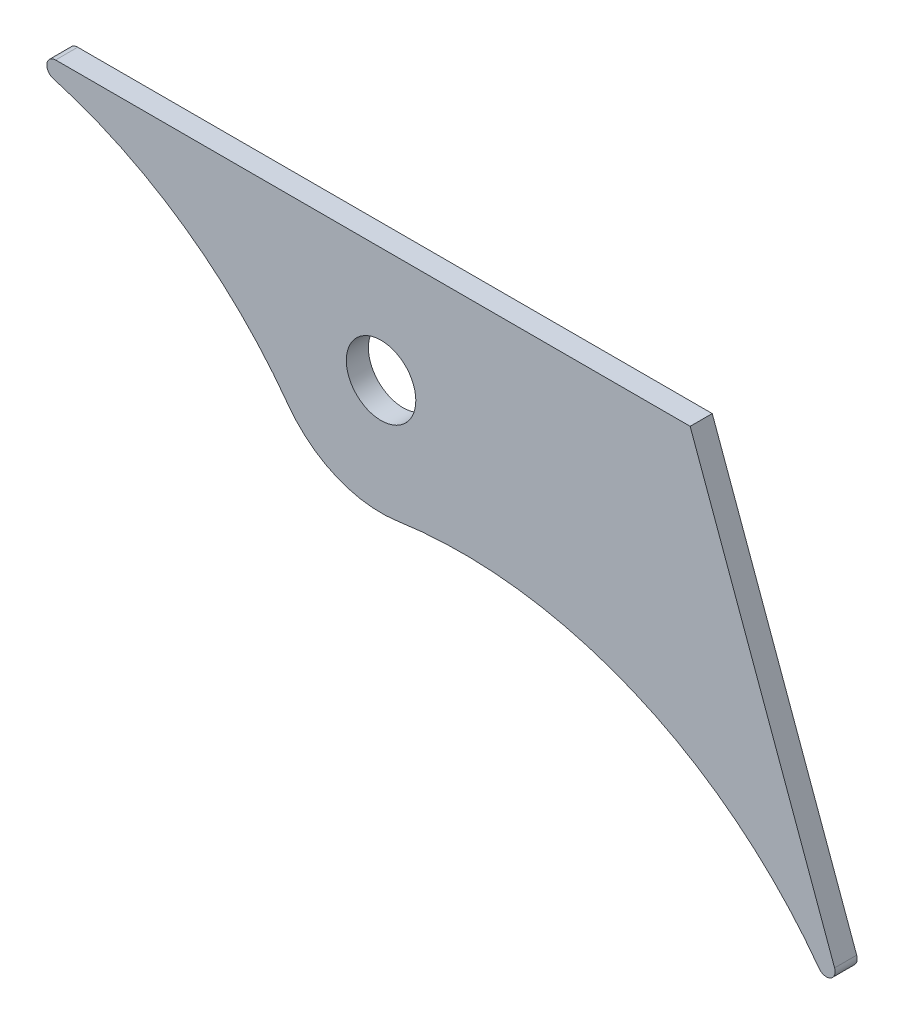
SolidWorks part; units mm, degrees
material "6061 Alloy"
ref_plane "Front Plane" through (0, 0, 0) normal (0, 0, 1) x (1, 0, 0)
ref_plane "Top Plane" through (0, 0, 0) normal (0, 1, 0) x (1, 0, 0)
ref_plane "Right Plane" through (0, 0, 0) normal (1, 0, 0) x (0, 0, -1)
sketch "Sketch1" plane through (0, 0, 0) normal (0, 0, 1) x (1, 0, 0)
  line L0 (0, 0) -> (-44.45, 0)
  line L1 (0, 0) -> (26.913, -73.9428)
  line L2 (-44.45, 0) -> (-109.2075, 0)
  circle A0 centre (-44.45, -16.51) radius 5
  arc A1 (-57.8127, -26.2063) -> (-42.0373, -32.8428) centre (-44.45, -16.51) ccw
  arc A2 (26.913, -73.9428) -> (-42.0373, -32.8428) centre (-32.7575, -95.661) ccw
  arc A3 (-57.8127, -26.2063) -> (-109.2075, 0) centre (-109.2075, -63.5) ccw
  dimension "D2" = 10
  dimension "D5" = 63.5
  dimension "D6" = 63.5
  dimension "D1" = 110
  dimension "D3" = 16.51
  dimension "D4" = 44.45
extrude "Boss-Extrude1" add sketch "Sketch1" along normal blind 3.175
fillet "Fillet1" radius 1.27 2 edges at (26.913, -73.9428, 1.5875) (-109.2075, 0, 1.5875)
